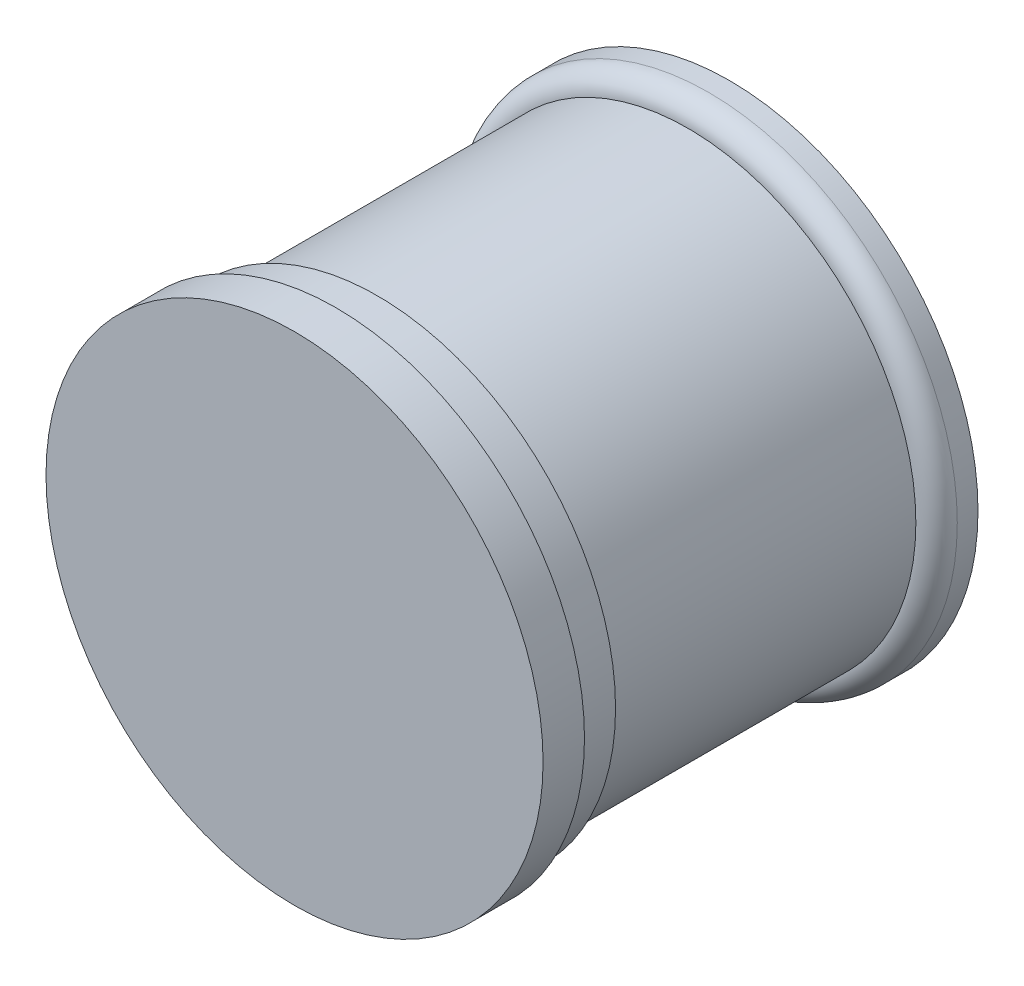
SolidWorks part; units mm, degrees
material "6061 Alloy"
ref_plane "Front" through (0, 0, 0) normal (0, 0, 1) x (1, 0, 0)
ref_plane "Top" through (0, 0, 0) normal (0, 1, 0) x (1, 0, 0)
ref_plane "Right" through (0, 0, 0) normal (1, 0, 0) x (0, 0, -1)
sketch "Sketch2" plane through (0, 0, 0) normal (0, 0, 1) x (1, 0, 0)
  circle A0 centre (0, 0) radius 600
  dimension "D1" = 1200
extrude "Boss-Extrude1" add sketch "Sketch2" along normal blind 100
sketch "Sketch3" plane through (0, 0, 100) normal (0, 0, 1) x (1, 0, 0)
  circle A0 centre (0, 0) radius 550
  dimension "D1" = 1100
extrude "Boss-Extrude2" add sketch "Sketch3" along normal blind 750
fillet "Fillet1" radius 50 1 edges at (600, 0, 100)
sketch "Sketch4" plane through (0, 0, 850) normal (0, 0, 1) x (1, 0, 0)
  circle A0 centre (0, 0) radius 575
  dimension "D1" = 1150
extrude "Boss-Extrude3" add sketch "Sketch4" along normal blind 100
sketch "Sketch5" plane through (0, 0, 950) normal (0, 0, 1) x (1, 0, 0)
  circle A0 centre (0, 0) radius 600
  dimension "D1" = 1200
extrude "Boss-Extrude4" add sketch "Sketch5" along normal blind 100
